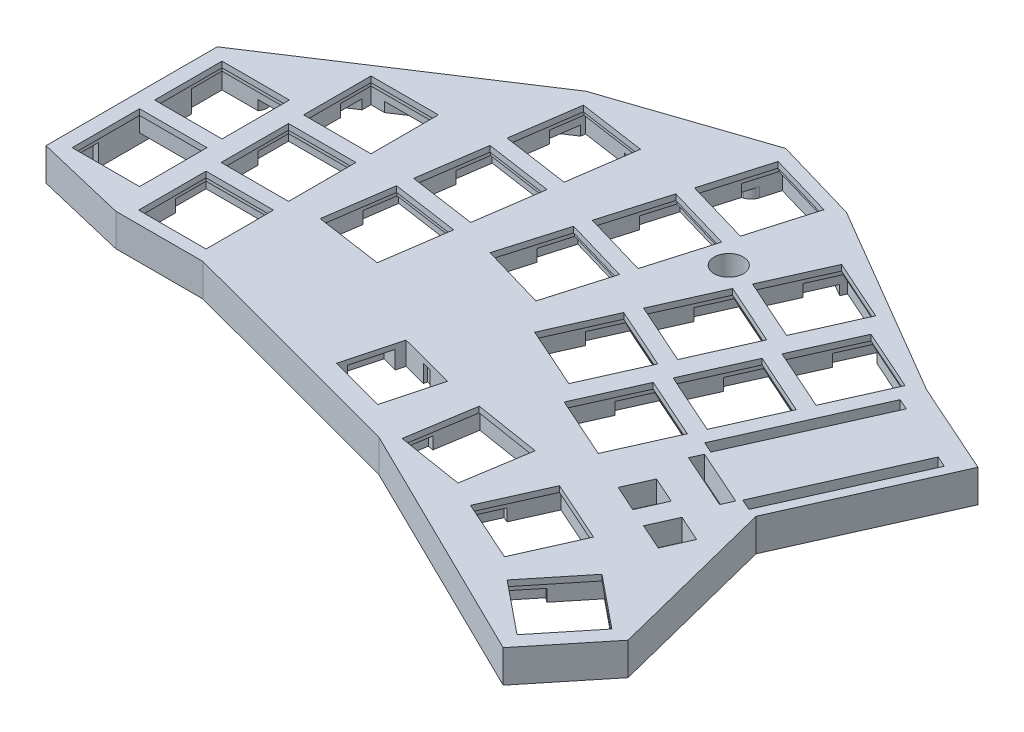
SolidWorks part; units mm, degrees
ref_plane "Front Plane" through (0, 0, 0) normal (0, 0, 1) x (1, 0, 0)
ref_plane "Top Plane" through (0, 0, 0) normal (0, 1, 0) x (1, 0, 0)
ref_plane "Right Plane" through (0, 0, 0) normal (1, 0, 0) x (0, 0, -1)
sketch "Ergogen Drawing" plane through (0, 0, 0) normal (0, 1, 0) x (1, 0, 0)
  line L0 (0.027, 17.9992) -> (18.027, 17.9992)
  line L1 (18.027, 17.9992) -> (18.027, -0.0008)
  line L2 (18.027, -0.0008) -> (0.027, -0.0008)
  line L3 (0.027, -0.0008) -> (0.027, 17.9992)
  line L4 (0.027, 34.9992) -> (18.027, 34.9992)
  line L5 (18.027, 34.9992) -> (18.027, 16.9992)
  line L6 (18.027, 16.9992) -> (0.027, 16.9992)
  line L7 (0.027, 16.9992) -> (0.027, 34.9992)
  line L8 (18.027, 15.9992) -> (36.027, 15.9992)
  line L9 (36.027, 15.9992) -> (36.027, -2.0008)
  line L10 (36.027, -2.0008) -> (18.027, -2.0008)
  line L11 (18.027, -2.0008) -> (18.027, 15.9992)
  line L12 (18.027, 32.9992) -> (36.027, 32.9992)
  line L13 (36.027, 32.9992) -> (36.027, 14.9992)
  line L14 (36.027, 14.9992) -> (18.027, 14.9992)
  line L15 (18.027, 14.9992) -> (18.027, 32.9992)
  line L16 (18.027, 49.9992) -> (36.027, 49.9992)
  line L17 (36.027, 49.9992) -> (36.027, 31.9992)
  line L18 (36.027, 31.9992) -> (18.027, 31.9992)
  line L19 (18.027, 31.9992) -> (18.027, 49.9992)
  line L20 (41.3768, 32.6051) -> (59.3329, 31.3495)
  line L21 (59.3329, 31.3495) -> (58.0773, 13.3933)
  line L22 (58.0773, 13.3933) -> (40.1211, 14.6489)
  line L23 (40.1211, 14.6489) -> (41.3768, 32.6051)
  line L24 (42.5626, 49.5637) -> (60.5188, 48.3081)
  line L25 (60.5188, 48.3081) -> (59.2631, 30.3519)
  line L26 (59.2631, 30.3519) -> (41.307, 31.6075)
  line L27 (41.307, 31.6075) -> (42.5626, 49.5637)
  line L28 (43.7485, 66.5223) -> (61.7046, 65.2667)
  line L29 (61.7046, 65.2667) -> (60.449, 47.3105)
  line L30 (60.449, 47.3105) -> (42.4929, 48.5661)
  line L31 (42.4929, 48.5661) -> (43.7485, 66.5223)
  line L32 (66.0898, 43.7082) -> (83.8507, 40.7838)
  line L33 (83.8507, 40.7838) -> (80.9263, 23.023)
  line L34 (80.9263, 23.023) -> (63.1655, 25.9473)
  line L35 (63.1655, 25.9473) -> (66.0898, 43.7082)
  line L36 (68.8517, 60.4823) -> (86.6126, 57.558)
  line L37 (86.6126, 57.558) -> (83.6882, 39.7971)
  line L38 (83.6882, 39.7971) -> (65.9274, 42.7215)
  line L39 (65.9274, 42.7215) -> (68.8517, 60.4823)
  line L40 (71.6136, 77.2565) -> (89.3745, 74.3321)
  line L41 (89.3745, 74.3321) -> (86.4501, 56.5713)
  line L42 (86.4501, 56.5713) -> (68.6893, 59.4956)
  line L43 (68.6893, 59.4956) -> (71.6136, 77.2565)
  line L44 (88.5581, 32.769) -> (105.9366, 28.0799)
  line L45 (105.9366, 28.0799) -> (101.2475, 10.7014)
  line L46 (101.2475, 10.7014) -> (83.869, 15.3905)
  line L47 (83.869, 15.3905) -> (88.5581, 32.769)
  line L48 (92.9866, 49.182) -> (110.3652, 44.4929)
  line L49 (110.3652, 44.4929) -> (105.6761, 27.1144)
  line L50 (105.6761, 27.1144) -> (88.2976, 31.8035)
  line L51 (88.2976, 31.8035) -> (92.9866, 49.182)
  line L52 (97.4152, 65.595) -> (114.7937, 60.906)
  line L53 (114.7937, 60.906) -> (110.1046, 43.5274)
  line L54 (110.1046, 43.5274) -> (92.7261, 48.2165)
  line L55 (92.7261, 48.2165) -> (97.4152, 65.595)
  line L56 (107.0448, 26.9674) -> (124.0477, 21.0597)
  line L57 (124.0477, 21.0597) -> (118.14, 4.0568)
  line L58 (118.14, 4.0568) -> (101.1371, 9.9645)
  line L59 (101.1371, 9.9645) -> (107.0448, 26.9674)
  line L60 (112.6243, 43.0257) -> (129.6273, 37.118)
  line L61 (129.6273, 37.118) -> (123.7195, 20.1151)
  line L62 (123.7195, 20.1151) -> (106.7166, 26.0228)
  line L63 (106.7166, 26.0228) -> (112.6243, 43.0257)
  line L64 (118.2039, 59.084) -> (135.2068, 53.1763)
  line L65 (135.2068, 53.1763) -> (129.299, 36.1734)
  line L66 (129.299, 36.1734) -> (112.2961, 42.0811)
  line L67 (112.2961, 42.0811) -> (118.2039, 59.084)
  line L68 (95.4197, 6.4051) -> (112.5714, 0.9445)
  line L69 (112.5714, 0.9445) -> (107.1108, -16.2072)
  line L70 (107.1108, -16.2072) -> (89.959, -10.7466)
  line L71 (89.959, -10.7466) -> (95.4197, 6.4051)
  line L72 (116.0129, -0.5249) -> (131.9353, -8.9198)
  line L73 (131.9353, -8.9198) -> (123.5404, -24.8423)
  line L74 (123.5404, -24.8423) -> (107.6179, -16.4473)
  line L75 (107.6179, -16.4473) -> (116.0129, -0.5249)
  line L76 (135.0644, -10.9721) -> (149.2602, -22.0392)
  line L77 (149.2602, -22.0392) -> (138.1931, -36.235)
  line L78 (138.1931, -36.235) -> (123.9973, -25.1679)
  line L79 (123.9973, -25.1679) -> (135.0644, -10.9721)
sketch "Layout Based on OG" plane through (0, 0, 0) normal (0, 1, 0) x (1, 0, 0)
  line L0 (0, 0) -> (0, 17) construction
  line L1 (0, 17) -> (18, 17) construction
  line L2 (18, 17) -> (18, 0) construction
  line L3 (18, 0) -> (0, 0) construction
  line L4 (2.05, 1.55) -> (2.05, 15.45)
  line L5 (2.05, 15.45) -> (15.95, 15.45)
  line L6 (15.95, 15.45) -> (15.95, 1.55)
  line L7 (15.95, 1.55) -> (2.05, 1.55)
  line L8 (109.1798, 58.6066) -> (27, -125.5436) construction
  line L9 (27, 46.7087) -> (27, -125.5436) construction
  line L10 (84.3863, 71.4039) -> (27, -125.5436) construction
  line L11 (54.2678, 62.3831) -> (27, -125.5436) construction
  line L12 (44.7261, 45.0233) -> (58.4821, 43.0274)
  line L13 (2.05, 18.55) -> (15.95, 18.55)
  line L14 (2.05, 18.55) -> (2.05, 32.45)
  line L15 (2.05, 32.45) -> (15.95, 32.45)
  line L16 (15.95, 18.55) -> (15.95, 32.45)
  line L17 (20.05, 31.2587) -> (33.95, 31.2587)
  line L18 (20.05, 31.2587) -> (20.05, 45.1587)
  line L19 (20.05, 45.1587) -> (33.95, 45.1587)
  line L20 (33.95, 31.2587) -> (33.95, 45.1587)
  line L21 (33.95, 28.1587) -> (20.05, 28.1587)
  line L22 (33.95, 28.1587) -> (33.95, 14.2587)
  line L23 (33.95, 14.2587) -> (20.05, 14.2587)
  line L24 (20.05, 28.1587) -> (20.05, 14.2587)
  line L25 (20.05, -2.7413) -> (33.95, -2.7413)
  line L26 (20.05, -2.7413) -> (20.05, 11.1587)
  line L27 (20.05, 11.1587) -> (33.95, 11.1587)
  line L28 (33.95, -2.7413) -> (33.95, 11.1587)
  line L29 (44.7261, 45.0233) -> (42.7302, 31.2674)
  line L30 (58.4821, 43.0274) -> (56.4861, 29.2714)
  line L31 (42.7302, 31.2674) -> (56.4861, 29.2714)
  line L32 (42.285, 28.1995) -> (56.041, 26.2036)
  line L33 (42.285, 28.1995) -> (40.2891, 14.4436)
  line L34 (56.041, 26.2036) -> (54.045, 12.4476)
  line L35 (40.2891, 14.4436) -> (54.045, 12.4476)
  line L36 (47.1672, 61.8472) -> (60.9232, 59.8512)
  line L37 (47.1672, 61.8472) -> (45.1712, 48.0912)
  line L38 (60.9232, 59.8512) -> (58.9272, 46.0953)
  line L39 (45.1712, 48.0912) -> (58.9272, 46.0953)
  line L40 (77.2802, 71.86) -> (90.6252, 67.9716)
  line L41 (77.2802, 71.86) -> (73.3917, 58.515)
  line L42 (90.6252, 67.9716) -> (86.7368, 54.6265)
  line L43 (73.3917, 58.515) -> (86.7368, 54.6265)
  line L44 (85.8695, 51.6503) -> (72.5245, 55.5388)
  line L45 (85.8695, 51.6503) -> (81.9811, 38.3053)
  line L46 (72.5245, 55.5388) -> (68.6361, 42.1937)
  line L47 (81.9811, 38.3053) -> (68.6361, 42.1937)
  line L48 (67.7688, 39.2175) -> (81.1139, 35.329)
  line L49 (67.7688, 39.2175) -> (63.8804, 25.8725)
  line L50 (81.1139, 35.329) -> (77.2254, 21.984)
  line L51 (63.8804, 25.8725) -> (77.2254, 21.984)
  line L52 (102.2015, 60.0235) -> (114.8949, 54.3589)
  line L53 (102.2015, 60.0235) -> (96.5369, 47.3301)
  line L54 (114.8949, 54.3589) -> (109.2302, 41.6655)
  line L55 (96.5369, 47.3301) -> (109.2302, 41.6655)
  line L56 (107.9669, 38.8346) -> (95.2735, 44.4992)
  line L57 (107.9669, 38.8346) -> (102.3023, 26.1412)
  line L58 (95.2735, 44.4992) -> (89.6089, 31.8058)
  line L59 (102.3023, 26.1412) -> (89.6089, 31.8058)
  line L60 (101.039, 23.3103) -> (88.3456, 28.9749)
  line L61 (101.039, 23.3103) -> (95.3744, 10.6169)
  line L62 (88.3456, 28.9749) -> (82.681, 16.2815)
  line L63 (95.3744, 10.6169) -> (82.681, 16.2815)
  line L64 (117.7053, 50.5958) -> (130.3987, 44.9312)
  line L65 (117.7053, 50.5958) -> (112.0407, 37.9024)
  line L66 (130.3987, 44.9312) -> (124.734, 32.2378)
  line L67 (112.0407, 37.9024) -> (124.734, 32.2378)
  line L68 (123.4707, 29.4069) -> (110.7773, 35.0715)
  line L69 (123.4707, 29.4069) -> (117.8061, 16.7135)
  line L70 (110.7773, 35.0715) -> (105.1127, 22.3782)
  line L71 (117.8061, 16.7135) -> (105.1127, 22.3782)
  line L72 (116.5428, 13.8826) -> (103.8494, 19.5473)
  line L73 (116.5428, 13.8826) -> (110.8782, 1.1892)
  line L74 (103.8494, 19.5473) -> (98.1848, 6.8539)
  line L75 (110.8782, 1.1892) -> (98.1848, 6.8539)
  line L76 (90.1692, -2.6429) -> (103.8962, -4.8292)
  line L77 (90.1692, -2.6429) -> (87.9829, -16.3699)
  line L78 (103.8962, -4.8292) -> (101.7099, -18.5562)
  line L79 (87.9829, -16.3699) -> (101.7099, -18.5562)
  line L80 (112.6329, -8.5638) -> (125.3263, -14.2284)
  line L81 (112.6329, -8.5638) -> (106.9683, -21.2572)
  line L82 (125.3263, -14.2284) -> (119.6617, -26.9218)
  line L83 (106.9683, -21.2572) -> (119.6617, -26.9218)
  line L84 (132.8305, -19.9983) -> (143.6253, -28.7552)
  line L85 (132.8305, -19.9983) -> (124.0737, -30.7931)
  line L86 (143.6253, -28.7552) -> (134.8684, -39.55)
  line L87 (124.0737, -30.7931) -> (134.8684, -39.55)
  line L88 (0, 0) -> (0, 34) construction
  line L89 (0, 34) -> (18, 46.7087) construction
  line L90 (18, 46.7087) -> (45.361, 63.6755) construction
  line L91 (45.361, 63.6755) -> (75.7456, 73.9216) construction
  line L92 (75.7456, 73.9216) -> (93.027, 68.8862) construction
  line L93 (93.027, 68.8862) -> (117.3986, 54.9389) construction
  line L94 (117.3986, 54.9389) -> (132.9024, 45.5112) construction
  line L95 (146.1938, -28.843) -> (135.484, -42.0452) construction
  line L96 (135.484, -42.0452) -> (85.7146, -17.5782) construction
  line L97 (0, 0) -> (18, -4.2913) construction
  line L98 (132.9024, 45.5112) -> (119.0465, 14.4627) construction
  line L99 (18, -4.2913) -> (36, -4.2913) construction
  line L100 (36, -4.2913) -> (85.7146, -17.5782) construction
  line L101 (119.0465, 14.4627) -> (137.3104, 6.3121) construction
  line L102 (137.3104, 6.3121) -> (151.1662, 37.3607) construction
  line L103 (151.1662, 37.3607) -> (132.9024, 45.5112) construction
  line L104 (146.1938, -28.843) -> (137.3104, 6.3121) construction
  line L105 (137.3104, 6.3121) -> (151.1662, 37.3607) construction
  line L106 (151.1662, 37.3607) -> (132.9024, 45.5112) construction
  line L107 (119.9597, 14.0551) -> (132.3892, 41.9075)
  line L108 (132.3892, 41.9075) -> (134.6722, 40.8887)
  line L109 (134.6722, 40.8887) -> (122.2427, 13.0363)
  line L110 (122.2427, 13.0363) -> (119.9597, 14.0551)
  line L111 (136.3972, 6.7197) -> (148.8267, 34.5721)
  line L112 (148.8267, 34.5721) -> (146.5437, 35.5909)
  line L113 (146.5437, 35.5909) -> (134.1142, 7.7385)
  line L114 (134.1142, 7.7385) -> (136.3972, 6.7197)
  line L115 (79.4058, -12.7868) -> (67.8127, -9.6883)
  line L116 (67.8127, -9.6883) -> (70.8336, 1.6149)
  line L117 (70.8336, 1.6149) -> (82.4267, -1.4835)
  line L118 (82.4267, -1.4835) -> (79.4058, -12.7868)
  line L119 (97.0327, -3.7361) -> (94.8464, -17.4631) construction
  line L120 (118.9913, -2.8379) -> (121.4364, 2.6412)
  line L121 (121.4364, 2.6412) -> (126.9156, 0.1961)
  line L122 (76.6302, 0.0657) -> (73.6092, -11.2375) construction
  line L123 (126.9156, 0.1961) -> (124.4704, -5.2831)
  line L124 (124.4704, -5.2831) -> (118.9913, -2.8379)
  line L125 (128.4611, -7.064) -> (130.9062, -1.5848)
  line L126 (130.9062, -1.5848) -> (136.3854, -4.03)
  line L127 (136.3854, -4.03) -> (133.9402, -9.5091)
  line L128 (133.9402, -9.5091) -> (128.4611, -7.064)
  line L137 (124.176, 1.4187) -> (121.7308, -4.0605) construction
  line L138 (133.6458, -2.8074) -> (131.2006, -8.2865) construction
  line L139 (126.7317, 7.1456) -> (128.1784, 10.3874) construction
  line L140 (135.0103, 42.8732) -> (147.795, 37.1678) construction
  line L141 (147.795, 37.1678) -> (133.1241, 4.2929) construction
  line L142 (133.1241, 4.2929) -> (120.3393, 9.9982) construction
  line L143 (120.3393, 9.9982) -> (135.0103, 42.8732) construction
  line L144 (120.9512, 9.7252) -> (121.97, 12.0082)
  line L145 (121.97, 12.0082) -> (133.531, 6.8489)
  line L146 (133.531, 6.8489) -> (132.5122, 4.5659)
  line L147 (132.5122, 4.5659) -> (120.9512, 9.7252)
  line L148 (126.9156, 0.1961) -> (140.3735, -5.8097) construction
  line L164 (-1, 34.5181) -> (-1, -0.7896)
  line L165 (-1, -0.7896) -> (17.8824, -5.2913)
  line L166 (17.8824, -5.2913) -> (35.8687, -5.2913)
  line L167 (35.8687, -5.2913) -> (85.3615, -18.5189)
  line L168 (85.3615, -18.5189) -> (135.7583, -43.2944)
  line L169 (135.7583, -43.2944) -> (147.2861, -29.0838)
  line L170 (147.2861, -29.0838) -> (138.3648, 6.2211)
  line L171 (138.3648, 6.2211) -> (152.487, 37.8664)
  line L172 (152.487, 37.8664) -> (133.3678, 46.3986)
  line L173 (133.3678, 46.3986) -> (117.9068, 55.8002) construction
  line L174 (117.9068, 55.8002) -> (93.4207, 69.8131) construction
  line L175 (93.4207, 69.8131) -> (75.7238, 74.9696)
  line L176 (75.7238, 74.9696) -> (44.9321, 64.5862)
  line L177 (44.9321, 64.5862) -> (17.4476, 47.5429) construction
  line L178 (17.4476, 47.5429) -> (-1, 34.5181) construction
  line L179 (-1, 34.5181) -> (44.9321, 64.5862)
  line L180 (133.3678, 46.3986) -> (93.4207, 69.8131)
  line L181 (27, -125.5436) -> (90.7493, 48.2155) construction
  circle A0 centre (143.0056, -24.3895) radius 2 construction
  circle A1 centre (143.0056, -24.3895) radius 1
  circle A2 centre (98.5143, -21.642) radius 2 construction
  circle A3 centre (98.5143, -21.642) radius 1
  circle A6 centre (17.05, -2.0087) radius 2 construction
  circle A7 centre (17.05, -2.0087) radius 1
  circle A8 centre (5.901, 35.45) radius 2 construction
  circle A9 centre (5.901, 35.45) radius 1
  circle A10 centre (72.7535, 70.802) radius 2 construction
  circle A11 centre (72.7535, 70.802) radius 1
  circle A12 centre (145.3286, 37.7757) radius 2 construction
  circle A13 centre (145.3286, 37.7757) radius 1
  circle A14 centre (90.7493, 48.2155) radius 3
  point P10 (110.8277, 18.1304)
  point P11 (117.7557, 33.6547)
  point P128 (75.1197, -5.5859)
  point P129 (95.9395, -10.5996)
  point P146 (127.7505, 9.4285)
  point P148 (128.1784, 10.3874)
  point P150 (122.9534, -1.3209)
  line B0 (18, 29.7087) -> (18, 46.7087) construction
  line B1 (18, 46.7087) -> (36, 46.7087) construction
  line B2 (36, 46.7087) -> (36, 29.7087) construction
  line B3 (36, 29.7087) -> (18, 29.7087) construction
  line B4 (20.05, 31.2587) -> (20.05, 45.1587) construction
  line B5 (20.05, 45.1587) -> (33.95, 45.1587) construction
  line B6 (33.95, 45.1587) -> (33.95, 31.2587) construction
  line B7 (33.95, 31.2587) -> (20.05, 31.2587) construction
  line B8 (18, 12.7087) -> (18, 29.7087) construction
  line B9 (18, 29.7087) -> (36, 29.7087) construction
  line B10 (36, 29.7087) -> (36, 12.7087) construction
  line B11 (36, 12.7087) -> (18, 12.7087) construction
  line B12 (20.05, 14.2587) -> (20.05, 28.1587) construction
  line B13 (20.05, 28.1587) -> (33.95, 28.1587) construction
  line B14 (33.95, 28.1587) -> (33.95, 14.2587) construction
  line B15 (33.95, 14.2587) -> (20.05, 14.2587) construction
  line B16 (18, -4.2913) -> (18, 12.7087) construction
  line B17 (18, 12.7087) -> (36, 12.7087) construction
  line B18 (36, 12.7087) -> (36, -4.2913) construction
  line B19 (36, -4.2913) -> (18, -4.2913) construction
  line B20 (20.05, -2.7413) -> (20.05, 11.1587) construction
  line B21 (20.05, 11.1587) -> (33.95, 11.1587) construction
  line B22 (33.95, 11.1587) -> (33.95, -2.7413) construction
  line B23 (33.95, -2.7413) -> (20.05, -2.7413) construction
  line B24 (42.9199, 46.8516) -> (45.361, 63.6755) construction
  line B25 (45.361, 63.6755) -> (63.1745, 61.0908) construction
  line B26 (63.1745, 61.0908) -> (60.7334, 44.267) construction
  line B27 (60.7334, 44.267) -> (42.9199, 46.8516) construction
  line B28 (45.1712, 48.0912) -> (47.1672, 61.8472) construction
  line B29 (47.1672, 61.8472) -> (60.9232, 59.8512) construction
  line B30 (60.9232, 59.8512) -> (58.9272, 46.0953) construction
  line B31 (58.9272, 46.0953) -> (45.1712, 48.0912) construction
  line B32 (40.4788, 30.0278) -> (42.9199, 46.8516) construction
  line B33 (42.9199, 46.8516) -> (60.7334, 44.267) construction
  line B34 (60.7334, 44.267) -> (58.2923, 27.4431) construction
  line B35 (58.2923, 27.4431) -> (40.4788, 30.0278) construction
  line B36 (42.7302, 31.2674) -> (44.7261, 45.0233) construction
  line B37 (44.7261, 45.0233) -> (58.4821, 43.0274) construction
  line B38 (58.4821, 43.0274) -> (56.4861, 29.2714) construction
  line B39 (56.4861, 29.2714) -> (42.7302, 31.2674) construction
  line B40 (38.0377, 13.204) -> (40.4788, 30.0278) construction
  line B41 (40.4788, 30.0278) -> (58.2923, 27.4431) construction
  line B42 (58.2923, 27.4431) -> (55.8512, 10.6193) construction
  line B43 (55.8512, 10.6193) -> (38.0377, 13.204) construction
  line B44 (40.2891, 14.4436) -> (42.285, 28.1995) construction
  line B45 (42.285, 28.1995) -> (56.041, 26.2036) construction
  line B46 (56.041, 26.2036) -> (54.045, 12.4476) construction
  line B47 (54.045, 12.4476) -> (40.2891, 14.4436) construction
  line B48 (70.99, 57.6004) -> (75.7456, 73.9216) construction
  line B49 (75.7456, 73.9216) -> (93.027, 68.8862) construction
  line B50 (93.027, 68.8862) -> (88.2713, 52.5649) construction
  line B51 (88.2713, 52.5649) -> (70.99, 57.6004) construction
  line B52 (73.3917, 58.515) -> (77.2802, 71.86) construction
  line B53 (77.2802, 71.86) -> (90.6252, 67.9716) construction
  line B54 (90.6252, 67.9716) -> (86.7368, 54.6265) construction
  line B55 (86.7368, 54.6265) -> (73.3917, 58.515) construction
  line B56 (66.2343, 41.2791) -> (70.99, 57.6004) construction
  line B57 (70.99, 57.6004) -> (88.2713, 52.5649) construction
  line B58 (88.2713, 52.5649) -> (83.5156, 36.2437) construction
  line B59 (83.5156, 36.2437) -> (66.2343, 41.2791) construction
  line B60 (68.6361, 42.1937) -> (72.5245, 55.5388) construction
  line B61 (72.5245, 55.5388) -> (85.8695, 51.6503) construction
  line B62 (85.8695, 51.6503) -> (81.9811, 38.3053) construction
  line B63 (81.9811, 38.3053) -> (68.6361, 42.1937) construction
  line B64 (61.4786, 24.9578) -> (66.2343, 41.2791) construction
  line B65 (66.2343, 41.2791) -> (83.5156, 36.2437) construction
  line B66 (83.5156, 36.2437) -> (78.76, 19.9224) construction
  line B67 (78.76, 19.9224) -> (61.4786, 24.9578) construction
  line B68 (63.8804, 25.8725) -> (67.7688, 39.2175) construction
  line B69 (67.7688, 39.2175) -> (81.1139, 35.329) construction
  line B70 (81.1139, 35.329) -> (77.2254, 21.984) construction
  line B71 (77.2254, 21.984) -> (63.8804, 25.8725) construction
  line B72 (80.1772, 15.7015) -> (87.1052, 31.2258) construction
  line B73 (87.1052, 31.2258) -> (103.5427, 23.8903) construction
  line B74 (103.5427, 23.8903) -> (96.6147, 8.366) construction
  line B75 (96.6147, 8.366) -> (80.1772, 15.7015) construction
  line B76 (82.681, 16.2815) -> (88.3456, 28.9749) construction
  line B77 (88.3456, 28.9749) -> (101.039, 23.3103) construction
  line B78 (101.039, 23.3103) -> (95.3744, 10.6169) construction
  line B79 (95.3744, 10.6169) -> (82.681, 16.2815) construction
  line B80 (87.1052, 31.2258) -> (94.0331, 46.7501) construction
  line B81 (94.0331, 46.7501) -> (110.4706, 39.4146) construction
  line B82 (110.4706, 39.4146) -> (103.5427, 23.8903) construction
  line B83 (103.5427, 23.8903) -> (87.1052, 31.2258) construction
  line B84 (89.6089, 31.8058) -> (95.2735, 44.4992) construction
  line B85 (95.2735, 44.4992) -> (107.9669, 38.8346) construction
  line B86 (107.9669, 38.8346) -> (102.3023, 26.1412) construction
  line B87 (102.3023, 26.1412) -> (89.6089, 31.8058) construction
  line B88 (94.0331, 46.7501) -> (100.9611, 62.2744) construction
  line B89 (100.9611, 62.2744) -> (117.3986, 54.9389) construction
  line B90 (117.3986, 54.9389) -> (110.4706, 39.4146) construction
  line B91 (110.4706, 39.4146) -> (94.0331, 46.7501) construction
  line B92 (96.5369, 47.3301) -> (102.2015, 60.0235) construction
  line B93 (102.2015, 60.0235) -> (114.8949, 54.3589) construction
  line B94 (114.8949, 54.3589) -> (109.2302, 41.6655) construction
  line B95 (109.2302, 41.6655) -> (96.5369, 47.3301) construction
  line B96 (109.5369, 37.3224) -> (116.4649, 52.8467) construction
  line B97 (116.4649, 52.8467) -> (132.9024, 45.5112) construction
  line B98 (132.9024, 45.5112) -> (125.9744, 29.9869) construction
  line B99 (125.9744, 29.9869) -> (109.5369, 37.3224) construction
  line B100 (112.0407, 37.9024) -> (117.7053, 50.5958) construction
  line B101 (117.7053, 50.5958) -> (130.3987, 44.9312) construction
  line B102 (130.3987, 44.9312) -> (124.734, 32.2378) construction
  line B103 (124.734, 32.2378) -> (112.0407, 37.9024) construction
  line B104 (102.609, 21.7981) -> (109.5369, 37.3224) construction
  line B105 (109.5369, 37.3224) -> (125.9744, 29.9869) construction
  line B106 (125.9744, 29.9869) -> (119.0465, 14.4627) construction
  line B107 (119.0465, 14.4627) -> (102.609, 21.7981) construction
  line B108 (105.1127, 22.3782) -> (110.7773, 35.0715) construction
  line B109 (110.7773, 35.0715) -> (123.4707, 29.4069) construction
  line B110 (123.4707, 29.4069) -> (117.8061, 16.7135) construction
  line B111 (117.8061, 16.7135) -> (105.1127, 22.3782) construction
  line B112 (95.6811, 6.2738) -> (102.609, 21.7981) construction
  line B113 (102.609, 21.7981) -> (119.0465, 14.4627) construction
  line B114 (119.0465, 14.4627) -> (112.1185, -1.0616) construction
  line B115 (112.1185, -1.0616) -> (95.6811, 6.2738) construction
  line B116 (98.1848, 6.8539) -> (103.8494, 19.5473) construction
  line B117 (103.8494, 19.5473) -> (116.5428, 13.8826) construction
  line B118 (116.5428, 13.8826) -> (110.8782, 1.1892) construction
  line B119 (110.8782, 1.1892) -> (98.1848, 6.8539) construction
  line B120 (104.4646, -21.8372) -> (111.3925, -6.3129) construction
  line B121 (111.3925, -6.3129) -> (127.83, -13.6484) construction
  line B122 (127.83, -13.6484) -> (120.9021, -29.1727) construction
  line B123 (120.9021, -29.1727) -> (104.4646, -21.8372) construction
  line B124 (106.9683, -21.2572) -> (112.6329, -8.5638) construction
  line B125 (112.6329, -8.5638) -> (125.3263, -14.2284) construction
  line B126 (125.3263, -14.2284) -> (119.6617, -26.9218) construction
  line B127 (119.6617, -26.9218) -> (106.9683, -21.2572) construction
  line B128 (85.7146, -17.5782) -> (88.3885, -0.7898) construction
  line B129 (88.3885, -0.7898) -> (106.1645, -3.621) construction
  line B130 (106.1645, -3.621) -> (103.4906, -20.4094) construction
  line B131 (103.4906, -20.4094) -> (85.7146, -17.5782) construction
  line B132 (87.9829, -16.3699) -> (90.1692, -2.6429) construction
  line B133 (90.1692, -2.6429) -> (103.8962, -4.8292) construction
  line B134 (103.8962, -4.8292) -> (101.7099, -18.5562) construction
  line B135 (101.7099, -18.5562) -> (87.9829, -16.3699) construction
  line B136 (121.5051, -30.7054) -> (132.215, -17.5031) construction
  line B137 (132.215, -17.5031) -> (146.1938, -28.843) construction
  line B138 (146.1938, -28.843) -> (135.484, -42.0452) construction
  line B139 (135.484, -42.0452) -> (121.5051, -30.7054) construction
  line B140 (124.0737, -30.7931) -> (132.8305, -19.9983) construction
  line B141 (132.8305, -19.9983) -> (143.6253, -28.7552) construction
  line B142 (143.6253, -28.7552) -> (134.8684, -39.55) construction
  line B143 (134.8684, -39.55) -> (124.0737, -30.7931) construction
  line B144 (0, 17) -> (0, 34) construction
  line B145 (0, 34) -> (18, 34) construction
  line B146 (18, 34) -> (18, 17) construction
  line B147 (18, 17) -> (0, 17) construction
  line B148 (2.05, 18.55) -> (2.05, 32.45) construction
  line B149 (2.05, 32.45) -> (15.95, 32.45) construction
  line B150 (15.95, 32.45) -> (15.95, 18.55) construction
  line B151 (15.95, 18.55) -> (2.05, 18.55) construction
  dimension "D46" = 4
  dimension "D47" = 2
  dimension "D48" = 3
  dimension "D52" = 4
  dimension "D53" = 2
  dimension "D54" = 4
  dimension "D55" = 2
  dimension "D57" = 4
  dimension "D58" = 2
  dimension "D60" = 4
  dimension "D61" = 2
  dimension "D63" = 4
  dimension "D64" = 2
  dimension "D51" = 3
  dimension "D83" = 6
  dimension "D1" = 18
  dimension "D2" = 17
  dimension "D3" = 13.9
  dimension "D4" = 13.9
  dimension "D5" = 2.05
  dimension "D6" = 1.55
  dimension "D7" = 205.1378
  dimension "D8" = 201.6553
  dimension "D9" = 189.8947
  dimension "D10" = 8.256
  dimension "D11" = 15
  dimension "D12" = 15
  dimension "D13" = 1.4278
  dimension "D14" = 0.974
  dimension "D15" = 1.5327
  dimension "D16" = 0.6031
  dimension "D17" = 5.9541
  dimension "D18" = 2.5593
  dimension "D19" = 7.805
  dimension "D20" = 7.989
  dimension "D21" = 172.2524
  dimension "D22" = 2.2911
  dimension "D23" = 4.2913
  dimension "D24" = 34
  dimension "D25" = 20
  dimension "D26" = 30.5
  dimension "D27" = 2.5
  dimension "D28" = 1
  dimension "D29" = 2.5
  dimension "D30" = 30.5
  dimension "D31" = 18
  dimension "D32" = 11.7
  dimension "D33" = 12
  dimension "D34" = 3
  dimension "D35" = 21.415
  dimension "D36" = 6
  dimension "D37" = 6
  dimension "D38" = 6
  dimension "D39" = 6
  dimension "D40" = 14
  dimension "D41" = 36
  dimension "D42" = 12.66
  dimension "D43" = 2.5
  dimension "D44" = 9.27
  dimension "D45" = 4.37
  dimension "D49" = 3
  dimension "D50" = 3
  dimension "D56" = 3
  dimension "D59" = 3
  dimension "D62" = 3
  dimension "D65" = 3
  dimension "D66" = 3
  dimension "D67" = 1
  dimension "D68" = 1
  dimension "D69" = 1
  dimension "D70" = 1
  dimension "D71" = 1
  dimension "D72" = 1
  dimension "D73" = 1
  dimension "D74" = 1
  dimension "D75" = 1
  dimension "D76" = 1
  dimension "D77" = 1
  dimension "D78" = 1
  dimension "D79" = 1
  dimension "D80" = 1
  dimension "D81" = 1
  dimension "D82" = 3.902
sketch_block_instance "Block-ChocSwitchCutout-3"
sketch_block "Block-ChocSwitchCutout" parameters "D1"=18, "D2"=17, "D3"=13.9, "D4"=13.9, "D5"=2.05, "D6"=1.55
sketch_block_instance "Block-ChocSwitchCutout-4"
sketch_block_instance "Block-ChocSwitchCutout-5"
sketch_block_instance "Block-ChocSwitchCutout-6"
sketch_block_instance "Block-ChocSwitchCutout-7"
sketch_block_instance "Block-ChocSwitchCutout-8"
sketch_block_instance "Block-ChocSwitchCutout-9"
sketch_block_instance "Block-ChocSwitchCutout-10"
sketch_block_instance "Block-ChocSwitchCutout-11"
sketch_block_instance "Block-ChocSwitchCutout-20"
sketch_block_instance "Block-ChocSwitchCutout-23"
sketch_block_instance "Block-ChocSwitchCutout-24"
sketch_block_instance "Block-ChocSwitchCutout-27"
sketch_block_instance "Block-ChocSwitchCutout-28"
sketch_block_instance "Block-ChocSwitchCutout-29"
sketch_block_instance "Block-ChocSwitchCutout-32"
sketch_block_instance "Block-ChocSwitchCutout-33"
sketch_block_instance "Block-ChocSwitchCutout-34"
sketch_block_instance "Block-ChocSwitchCutout-37"
other "AlignGroup1"
extrude "Top Plate" add sketch "Layout Based on OG" along normal blind 1.2 contours L105 L106 L94 L93 L92 L91 L90 L89 L88 L97 L99 L100 L96 L95 L104 L73 L75 L74 L72 L69 L71 L70 L68 L61 L63 L62 L60 L57 L59 L58 L56 L45 L47 L46 L44 L6 L7 L4 L5 L16 L13 L14 L15 | A9 | A7 | A3 | A1 | A13 | A11 region at (81.1823, 0, -18.7965) region at (143.0056, 0, 24.3895) region at (98.5143, 0, 21.642) region at (17.05, 0, 2.0087) region at (5.901, 0, -35.45) region at (72.7535, 0, -70.802) region at (145.3286, 0, -37.7757)
sketch "Sketch1" plane through (0, 0, 0) normal (0, -1, 0) x (1, 0, 0)
  line L0 (124.9363, -31.7095) -> (130.927, -45.1335)
  line L1 (130.927, -45.1335) -> (117.503, -51.1241)
  line L2 (117.503, -51.1241) -> (111.5124, -37.7002)
  line L3 (111.5124, -37.7002) -> (124.9363, -31.7095)
  line L4 (118.0084, -16.1852) -> (123.999, -29.6092)
  line L5 (117.7053, -50.5958) -> (130.3987, -44.9312) construction
  line L6 (123.999, -29.6092) -> (110.5751, -35.5998)
  line L7 (117.7053, -50.5958) -> (112.0407, -37.9024) construction
  line L8 (110.5751, -35.5998) -> (104.5844, -22.1759)
  line L9 (104.5844, -22.1759) -> (118.0084, -16.1852)
  line L10 (123.4707, -29.4069) -> (117.8061, -16.7135) construction
  line L11 (111.0804, -0.661) -> (117.0711, -14.0849)
  line L12 (117.8061, -16.7135) -> (105.1127, -22.3782) construction
  line L13 (117.0711, -14.0849) -> (103.6471, -20.0755)
  line L14 (103.6471, -20.0755) -> (97.6565, -6.6516)
  line L15 (97.6565, -6.6516) -> (111.0804, -0.661)
  line L16 (103.8494, -19.5473) -> (98.1848, -6.8539) construction
  line L17 (110.8782, -1.1892) -> (98.1848, -6.8539) construction
  line L18 (95.5766, -10.0886) -> (101.5673, -23.5126)
  line L19 (101.5673, -23.5126) -> (88.1433, -29.5032)
  line L20 (88.1433, -29.5032) -> (82.1527, -16.0793)
  line L21 (82.1527, -16.0793) -> (95.5766, -10.0886)
  line L22 (101.039, -23.3103) -> (88.3456, -28.9749) construction
  line L23 (101.039, -23.3103) -> (95.3744, -10.6169) construction
  line L24 (102.5046, -25.6129) -> (108.4952, -39.0369)
  line L25 (108.4952, -39.0369) -> (95.0713, -45.0275)
  line L26 (95.0713, -45.0275) -> (89.0806, -31.6036)
  line L27 (89.0806, -31.6036) -> (102.5046, -25.6129)
  line L28 (102.3023, -26.1412) -> (89.6089, -31.8058) construction
  line L29 (95.2735, -44.4992) -> (89.6089, -31.8058) construction
  line L30 (109.4325, -41.1372) -> (115.4231, -54.5612)
  line L31 (115.4231, -54.5612) -> (101.9992, -60.5518)
  line L32 (101.9992, -60.5518) -> (96.0086, -47.1279)
  line L33 (96.0086, -47.1279) -> (109.4325, -41.1372)
  line L34 (102.2015, -60.0235) -> (114.8949, -54.3589) construction
  line L35 (114.8949, -54.3589) -> (109.2302, -41.6655) construction
  line L36 (119.864, 27.4501) -> (125.8546, 14.0261)
  line L37 (125.8546, 14.0261) -> (112.4307, 8.0355)
  line L38 (112.4307, 8.0355) -> (106.44, 21.4594)
  line L39 (106.44, 21.4594) -> (119.864, 27.4501)
  line L40 (125.3263, 14.2284) -> (119.6617, 26.9218) construction
  line L41 (106.9683, 21.2572) -> (119.6617, 26.9218) construction
  line L42 (144.1879, 28.6966) -> (134.9271, 40.1126)
  line L43 (134.9271, 40.1126) -> (123.511, 30.8517)
  line L44 (123.511, 30.8517) -> (132.7719, 19.4357)
  line L45 (132.7719, 19.4357) -> (144.1879, 28.6966)
  line L46 (143.6253, 28.7552) -> (134.8684, 39.55) construction
  line L47 (132.8305, 19.9983) -> (143.6253, 28.7552) construction
  line L48 (132.8305, 19.9983) -> (124.0737, 30.7931) construction
  line L49 (104.3541, 4.4971) -> (102.042, 19.0142)
  line L50 (102.042, 19.0142) -> (87.5249, 16.702)
  line L51 (87.5249, 16.702) -> (89.8371, 2.185)
  line L52 (89.8371, 2.185) -> (104.3541, 4.4971)
  line L61 (86.3655, -51.9224) -> (82.2532, -37.8093)
  line L62 (103.8962, 4.8292) -> (101.7099, 18.5562) construction
  line L63 (82.2532, -37.8093) -> (68.1401, -41.9216)
  line L64 (87.9829, 16.3699) -> (101.7099, 18.5562) construction
  line L65 (91.1211, -68.2437) -> (87.0089, -54.1306)
  line L66 (87.0089, -54.1306) -> (72.8958, -58.2429)
  line L67 (72.8958, -58.2429) -> (77.008, -72.3559)
  line L68 (77.008, -72.3559) -> (91.1211, -68.2437)
  line L69 (61.3764, -60.1896) -> (59.2656, -45.642)
  line L70 (59.2656, -45.642) -> (44.718, -47.7528)
  line L71 (44.718, -47.7528) -> (46.8288, -62.3005)
  line L72 (46.8288, -62.3005) -> (61.3764, -60.1896)
  line L73 (34.35, -45.5587) -> (34.35, -30.8587)
  line L74 (34.35, -30.8587) -> (19.65, -30.8587)
  line L75 (19.65, -30.8587) -> (19.65, -45.5587)
  line L76 (19.65, -45.5587) -> (34.35, -45.5587)
  line L77 (90.6252, -67.9716) -> (86.7368, -54.6265) construction
  line L78 (47.1672, -61.8472) -> (45.1712, -48.0912) construction
  line L79 (33.95, -31.2587) -> (33.95, -45.1587) construction
  line L80 (73.3917, -58.515) -> (86.7368, -54.6265) construction
  line L81 (60.9232, -59.8512) -> (58.9272, -46.0953) construction
  line L82 (45.1712, -48.0912) -> (58.9272, -46.0953) construction
  line L83 (68.1401, -41.9216) -> (72.2524, -56.0347)
  line L84 (20.05, -31.2587) -> (33.95, -31.2587) construction
  line L85 (72.2524, -56.0347) -> (86.3655, -51.9224)
  line L86 (85.8695, -51.6503) -> (81.9811, -38.3053) construction
  line L87 (81.9811, -38.3053) -> (68.6361, -42.1937) construction
  line L88 (81.6098, -35.6012) -> (77.4976, -21.4881)
  line L89 (77.4976, -21.4881) -> (63.3845, -25.6003)
  line L90 (63.3845, -25.6003) -> (67.4967, -39.7134)
  line L91 (67.4967, -39.7134) -> (81.6098, -35.6012)
  line L92 (81.1139, -35.329) -> (77.2254, -21.984) construction
  line L93 (63.8804, -25.8725) -> (77.2254, -21.984) construction
  line L94 (58.9353, -43.3658) -> (56.8245, -28.8181)
  line L95 (56.8245, -28.8181) -> (42.2769, -30.929)
  line L96 (42.2769, -30.929) -> (44.3877, -45.4766)
  line L97 (44.3877, -45.4766) -> (58.9353, -43.3658)
  line L98 (58.4821, -43.0274) -> (56.4861, -29.2714) construction
  line L99 (42.7302, -31.2674) -> (56.4861, -29.2714) construction
  line L100 (56.4943, -26.542) -> (54.3834, -11.9943)
  line L101 (54.3834, -11.9943) -> (39.8358, -14.1052)
  line L102 (39.8358, -14.1052) -> (41.9466, -28.6528)
  line L103 (41.9466, -28.6528) -> (56.4943, -26.542)
  line L104 (56.041, -26.2036) -> (54.045, -12.4476) construction
  line L105 (40.2891, -14.4436) -> (54.045, -12.4476) construction
  line L106 (34.35, -28.5587) -> (34.35, -13.8587)
  line L107 (34.35, -13.8587) -> (19.65, -13.8587)
  line L108 (19.65, -13.8587) -> (19.65, -28.5587)
  line L109 (19.65, -28.5587) -> (34.35, -28.5587)
  line L110 (33.95, -28.1587) -> (33.95, -14.2587) construction
  line L111 (33.95, -14.2587) -> (20.05, -14.2587) construction
  line L112 (34.35, -11.5587) -> (34.35, 3.1413)
  line L113 (34.35, 3.1413) -> (19.65, 3.1413)
  line L114 (19.65, 3.1413) -> (19.65, -11.5587)
  line L115 (19.65, -11.5587) -> (34.35, -11.5587)
  line L116 (20.05, 2.7413) -> (33.95, 2.7413) construction
  line L117 (20.05, 2.7413) -> (20.05, -11.1587) construction
  line L118 (16.35, -15.85) -> (16.35, -1.15)
  line L119 (16.35, -1.15) -> (1.65, -1.15)
  line L120 (1.65, -1.15) -> (1.65, -15.85)
  line L121 (1.65, -15.85) -> (16.35, -15.85)
  line L122 (2.05, -1.55) -> (2.05, -15.45) construction
  line L123 (15.95, -1.55) -> (2.05, -1.55) construction
  line L124 (16.35, -32.85) -> (16.35, -18.15)
  line L125 (16.35, -18.15) -> (1.65, -18.15)
  line L126 (1.65, -18.15) -> (1.65, -32.85)
  line L127 (1.65, -32.85) -> (16.35, -32.85)
  line L128 (2.05, -18.55) -> (2.05, -32.45) construction
  line L129 (2.05, -18.55) -> (15.95, -18.55) construction
  dimension "D1" = 14.7
  dimension "D2" = 14.7
  dimension "D3" = 0.4
  dimension "D4" = 0.4
  dimension "D5" = 14.7
  dimension "D6" = 14.7
  dimension "D7" = 0.4
  dimension "D8" = 0.4
  dimension "D9" = 14.7
  dimension "D10" = 14.7
  dimension "D11" = 0.4
  dimension "D12" = 0.4
  dimension "D13" = 14.7
  dimension "D14" = 14.7
  dimension "D15" = 0.4
  dimension "D16" = 0.4
  dimension "D17" = 14.7
  dimension "D18" = 14.7
  dimension "D19" = 0.4
  dimension "D20" = 0.4
  dimension "D21" = 14.7
  dimension "D22" = 0.4
  dimension "D23" = 0.4
  dimension "D24" = 14.7
  dimension "D25" = 14.7
  dimension "D26" = 14.7
  dimension "D27" = 0.4
  dimension "D28" = 0.4
  dimension "D29" = 14.7
  dimension "D30" = 14.7
  dimension "D31" = 0.4
  dimension "D32" = 0.4
  dimension "D33" = 14.7
  dimension "D34" = 14.7
  dimension "D35" = 0.4
  dimension "D36" = 0.4
  dimension "D37" = 0.4
  dimension "D38" = 0.4
  dimension "D39" = 14.7
  dimension "D40" = 14.7
  dimension "D41" = 0.4
  dimension "D42" = 0.4
  dimension "D43" = 14.7
  dimension "D44" = 14.7
  dimension "D45" = 14.7
  dimension "D46" = 0.4
  dimension "D47" = 0.4
  dimension "D48" = 14.7
  dimension "D49" = 14.7
  dimension "D50" = 14.7
  dimension "D51" = 0.4
  dimension "D52" = 0.4
  dimension "D53" = 14.7
  dimension "D54" = 14.7
  dimension "D55" = 0.4
  dimension "D56" = 0.4
  dimension "D57" = 14.7
  dimension "D58" = 14.7
  dimension "D59" = 0.4
  dimension "D60" = 0.4
  dimension "D61" = 14.7
  dimension "D62" = 14.7
  dimension "D63" = 0.4
  dimension "D64" = 0.4
  dimension "D65" = 14.7
  dimension "D66" = 14.7
  dimension "D67" = 0.4
  dimension "D68" = 0.4
  dimension "D69" = 14.7
  dimension "D70" = 14.7
  dimension "D71" = 0.4
  dimension "D72" = 0.4
  dimension "D73" = 14.7
  dimension "D74" = 14.7
  dimension "D75" = 0.4
  dimension "D76" = 0.4
  dimension "D77" = 14.7
  dimension "D78" = 14.7
  dimension "D79" = 0.4
  dimension "D80" = 0.4
extrude "Boss-Extrude2" add sketch "Layout Based on OG<7>" against normal blind 5.5 contours L172 L180 L175 L176 L179 L164 L165 L166 L167 L168 L169 L170 L171 A13 A11 A9 A7 A3 A1 L146 L147 L144 L145 L127 L128 L125 L126 L123 L124 L120 L121 L117 L118 L115 L116 L109 L110 L107 L108 region at (81.1823, 0, -18.7965)
sketch "Layout Based on OG<7>" plane through (0, 0, 0) normal (0, 1, 0) x (1, 0, 0) same geometry as "Layout Based on OG"
extrude "Cut-Extrude1" cut sketch "Sketch1" along normal blind 5.5
sketch "Sketch4" plane through (0, -5.5, 0) normal (0, -1, 0) x (1, 0, 0)
  line L0 (74.3817, 12.2203) -> (77.7899, -0.5321)
  line L1 (77.7899, -0.5321) -> (75.8577, -1.0485)
  line L2 (75.8577, -1.0485) -> (72.4495, 11.7039)
  line L3 (72.4495, 11.7039) -> (74.3817, 12.2203)
  line L4 (67.8127, 9.6883) -> (70.8336, -1.6149) construction
  line L6 (79.4058, 12.7868) -> (67.8127, 9.6883) construction
  line L8 (82.4267, 1.4835) -> (79.4058, 12.7868) construction
  line L9 (83.0232, 11.8386) -> (85.0888, 4.1099)
  line L10 (85.0888, 4.1099) -> (76.394, 1.7861)
  line L11 (76.394, 1.7861) -> (67.2162, -0.6668)
  line L12 (67.2162, -0.6668) -> (65.1505, 7.0619)
  line L14 (83.0232, 11.8386) -> (74.3284, 9.5148)
  line L15 (74.3284, 9.5148) -> (65.1505, 7.0619)
  dimension "D1" = 2
  dimension "D2" = 13.2
  dimension "D3" = 0.75
  dimension "D4" = 5
  dimension "D5" = 9
  dimension "D6" = 9.5
  dimension "D7" = 3.25
  dimension "D8" = 8
  dimension "D9" = 1.85
  dimension "D10" = 9
extrude "Cut-Extrude2" cut sketch "Sketch4" against normal blind 5.7 contours L9 L14 L0 L10 | L2 L15 L12 L11 | L10 L11 L2 L1 L0 | L15 L14 L0 L3 L2 region at (73.7512, -5.5, 10.7062) region at (80.0709, -5.5, 6.9092) region at (76.4882, -5.5, 0.4656) region at (70.1685, -5.5, 4.2626)
sketch "Sketch5" plane through (0, -5.5, 0) normal (0, -1, 0) x (1, 0, 0)
  line L0 (90.4768, -61.9215) -> (92.5469, -69.0261)
  line L1 (92.5469, -69.0261) -> (76.2257, -73.7817)
  line L2 (76.2257, -73.7817) -> (74.1556, -66.6772)
  line L3 (74.1556, -66.6772) -> (90.4768, -61.9215)
  line L4 (91.1211, -68.2437) -> (87.0089, -54.1306) construction
  line L5 (80.9655, -29.279) -> (83.0356, -36.3835)
  line L6 (83.0356, -36.3835) -> (66.7143, -41.1392)
  line L7 (66.7143, -41.1392) -> (64.6442, -34.0347)
  line L8 (64.6442, -34.0347) -> (80.9655, -29.279)
  line L9 (72.2524, -56.0347) -> (86.3655, -51.9224) construction
  line L10 (77.008, -72.3559) -> (91.1211, -68.2437) construction
  line L11 (85.7211, -45.6003) -> (87.7913, -52.7048)
  line L12 (87.7913, -52.7048) -> (71.47, -57.4605)
  line L13 (71.47, -57.4605) -> (69.3999, -50.3559)
  line L14 (69.3999, -50.3559) -> (85.7211, -45.6003)
  line L15 (68.1401, -41.9216) -> (72.2524, -56.0347) construction
  line L16 (81.6098, -35.6012) -> (77.4976, -21.4881) construction
  line L17 (67.4967, -39.7134) -> (81.6098, -35.6012) construction
  line L18 (113.9263, -48.385) -> (116.942, -55.1427)
  line L19 (116.942, -55.1427) -> (101.4177, -62.0706)
  line L20 (101.4177, -62.0706) -> (98.402, -55.313)
  line L21 (98.402, -55.313) -> (113.9263, -48.385)
  line L22 (96.0086, -47.1279) -> (101.9992, -60.5518) construction
  line L23 (106.9983, -32.8608) -> (110.014, -39.6184)
  line L24 (110.014, -39.6184) -> (94.4897, -46.5463)
  line L25 (94.4897, -46.5463) -> (91.474, -39.7887)
  line L26 (91.474, -39.7887) -> (106.9983, -32.8608)
  line L27 (100.0704, -17.3365) -> (103.0861, -24.0941)
  line L28 (103.0861, -24.0941) -> (87.5618, -31.022)
  line L29 (87.5618, -31.022) -> (84.5461, -24.2644)
  line L30 (84.5461, -24.2644) -> (100.0704, -17.3365)
  line L31 (115.5742, -7.9088) -> (118.5899, -14.6664)
  line L32 (118.5899, -14.6664) -> (103.0656, -21.5944)
  line L33 (103.0656, -21.5944) -> (100.0499, -14.8367)
  line L34 (100.0499, -14.8367) -> (115.5742, -7.9088)
  line L35 (122.5021, -23.4331) -> (125.5178, -30.1907)
  line L36 (125.5178, -30.1907) -> (109.9935, -37.1187)
  line L37 (109.9935, -37.1187) -> (106.9778, -30.361)
  line L38 (106.9778, -30.361) -> (122.5021, -23.4331)
  line L39 (129.4301, -38.9574) -> (132.4458, -45.715)
  line L40 (132.4458, -45.715) -> (116.9215, -52.6429)
  line L41 (116.9215, -52.6429) -> (113.9058, -45.8853)
  line L42 (113.9058, -45.8853) -> (129.4301, -38.9574)
  line L43 (130.927, -45.1335) -> (124.9363, -31.7095) construction
  line L44 (117.503, -51.1241) -> (130.927, -45.1335) construction
  line L45 (115.4231, -54.5612) -> (109.4325, -41.1372) construction
  line L46 (101.9992, -60.5518) -> (115.4231, -54.5612) construction
  line L47 (89.0806, -31.6036) -> (95.0713, -45.0275) construction
  line L48 (95.0713, -45.0275) -> (108.4952, -39.0369) construction
  line L49 (88.1433, -29.5032) -> (101.5673, -23.5126) construction
  line L50 (101.5673, -23.5126) -> (95.5766, -10.0886) construction
  line L51 (117.0711, -14.0849) -> (111.0804, -0.661) construction
  line L52 (103.6471, -20.0755) -> (117.0711, -14.0849) construction
  line L53 (123.999, -29.6092) -> (118.0084, -16.1852) construction
  line L54 (110.5751, -35.5998) -> (123.999, -29.6092) construction
  line L55 (61.6171, -53.8393) -> (62.6797, -61.1626)
  line L56 (62.6797, -61.1626) -> (45.8558, -63.6037)
  line L57 (45.8558, -63.6037) -> (44.7932, -56.2804)
  line L58 (44.7932, -56.2804) -> (61.6171, -53.8393)
  line L59 (61.3764, -60.1896) -> (59.2656, -45.642) construction
  line L60 (59.176, -37.0154) -> (60.2386, -44.3387)
  line L61 (60.2386, -44.3387) -> (43.4147, -46.7798)
  line L62 (43.4147, -46.7798) -> (42.3521, -39.4565)
  line L63 (42.3521, -39.4565) -> (59.176, -37.0154)
  line L64 (56.7349, -20.1916) -> (57.7975, -27.5149)
  line L65 (57.7975, -27.5149) -> (40.9736, -29.956)
  line L66 (40.9736, -29.956) -> (39.911, -22.6327)
  line L67 (39.911, -22.6327) -> (56.7349, -20.1916)
  line L68 (35.5, -39.3087) -> (35.5, -46.7087)
  line L69 (35.5, -46.7087) -> (18.5, -46.7087)
  line L70 (18.5, -46.7087) -> (18.5, -39.3087)
  line L71 (18.5, -39.3087) -> (35.5, -39.3087)
  line L72 (34.35, -45.5587) -> (34.35, -30.8587) construction
  line L73 (35.5, -22.3087) -> (35.5, -29.7087)
  line L74 (35.5, -29.7087) -> (18.5, -29.7087)
  line L75 (18.5, -29.7087) -> (18.5, -22.3087)
  line L76 (18.5, -22.3087) -> (35.5, -22.3087)
  line L77 (17.5, -26.6) -> (17.5, -34)
  line L78 (17.5, -34) -> (0.5, -34)
  line L79 (0.5, -34) -> (0.5, -26.6)
  line L80 (0.5, -26.6) -> (17.5, -26.6)
  line L81 (17.5, 0) -> (17.5, -7.4)
  line L82 (17.5, -7.4) -> (0.5, -7.4)
  line L83 (0.5, -7.4) -> (0.5, 0)
  line L84 (0.5, 0) -> (17.5, 0)
  line L85 (35.5, -5.3087) -> (35.5, -12.7087)
  line L86 (35.5, -12.7087) -> (18.5, -12.7087)
  line L87 (18.5, -12.7087) -> (18.5, -5.3087)
  line L88 (18.5, -5.3087) -> (35.5, -5.3087)
  line L89 (46.8288, -62.3005) -> (61.3764, -60.1896) construction
  line L90 (58.9353, -43.3658) -> (56.8245, -28.8181) construction
  line L91 (44.3877, -45.4766) -> (58.9353, -43.3658) construction
  line L92 (41.9466, -28.6528) -> (56.4943, -26.542) construction
  line L93 (39.8358, -14.1052) -> (41.9466, -28.6528) construction
  line L94 (19.65, -45.5587) -> (34.35, -45.5587) construction
  line L95 (19.65, -30.8587) -> (19.65, -45.5587) construction
  line L96 (19.65, -28.5587) -> (34.35, -28.5587) construction
  line L97 (34.35, -28.5587) -> (34.35, -13.8587) construction
  line L98 (19.65, -11.5587) -> (34.35, -11.5587) construction
  line L99 (19.65, 3.1413) -> (19.65, -11.5587) construction
  line L101 (1.65, -1.15) -> (1.65, -15.85) construction
  line L102 (1.65, -32.85) -> (16.35, -32.85) construction
  line L103 (1.65, -18.15) -> (1.65, -32.85) construction
  line L104 (120.4455, 28.9689) -> (123.4612, 22.2113)
  line L105 (123.4612, 22.2113) -> (107.9369, 15.2833)
  line L106 (107.9369, 15.2833) -> (104.9212, 22.0409)
  line L107 (104.9212, 22.0409) -> (120.4455, 28.9689)
  line L108 (102.9968, 20.3307) -> (104.1607, 13.0228)
  line L109 (104.1607, 13.0228) -> (87.3723, 10.3489)
  line L110 (87.3723, 10.3489) -> (86.2084, 17.6568)
  line L111 (86.2084, 17.6568) -> (102.9968, 20.3307)
  line L112 (135.0957, 41.7302) -> (139.7576, 35.9834)
  line L113 (139.7576, 35.9834) -> (126.5554, 25.2735)
  line L114 (126.5554, 25.2735) -> (121.8934, 31.0203)
  line L115 (121.8934, 31.0203) -> (135.0957, 41.7302)
  line L116 (87.5249, 16.702) -> (89.8371, 2.185) construction
  line L117 (123.511, 30.8517) -> (132.7719, 19.4357) construction
  line L118 (106.44, 21.4594) -> (112.4307, 8.0355) construction
  line L119 (102.042, 19.0142) -> (87.5249, 16.702) construction
  line L120 (119.864, 27.4501) -> (106.44, 21.4594) construction
  line L121 (134.9271, 40.1126) -> (123.511, 30.8517) construction
  line L122 (16.35, -1.15) -> (1.65, -1.15) construction
  point P156 (106.429, 18.6621)
  dimension "D1" = 17
  dimension "D2" = 7.4
  dimension "D3" = 1.15
  dimension "D4" = 1.15
  dimension "D5" = 17
  dimension "D6" = 7.4
  dimension "D7" = 17
  dimension "D8" = 7.4
  dimension "D9" = 1.15
  dimension "D10" = 1.15
  dimension "D11" = 1.15
  dimension "D12" = 1.15
  dimension "D13" = 17
  dimension "D14" = 7.4
  dimension "D15" = 17
  dimension "D16" = 7.4
  dimension "D17" = 17
  dimension "D18" = 7.4
  dimension "D19" = 17
  dimension "D20" = 7.4
  dimension "D21" = 17
  dimension "D22" = 7.4
  dimension "D23" = 17
  dimension "D24" = 7.4
  dimension "D25" = 1.15
  dimension "D26" = 1.15
  dimension "D27" = 1.15
  dimension "D28" = 1.15
  dimension "D29" = 1.15
  dimension "D30" = 1.15
  dimension "D31" = 1.15
  dimension "D32" = 1.15
  dimension "D33" = 1.15
  dimension "D34" = 1.15
  dimension "D35" = 1.15
  dimension "D36" = 1.15
  dimension "D37" = 17
  dimension "D38" = 7.4
  dimension "D39" = 17
  dimension "D40" = 7.4
  dimension "D41" = 17
  dimension "D42" = 7.4
  dimension "D43" = 17
  dimension "D44" = 7.4
  dimension "D45" = 17
  dimension "D46" = 7.4
  dimension "D47" = 17
  dimension "D48" = 7.4
  dimension "D49" = 17
  dimension "D50" = 7.4
  dimension "D51" = 17
  dimension "D52" = 7.4
  dimension "D53" = 1.15
  dimension "D54" = 1.15
  dimension "D55" = 1.15
  dimension "D56" = 1.15
  dimension "D57" = 1.15
  dimension "D58" = 1.15
  dimension "D59" = 1.15
  dimension "D60" = 1.15
  dimension "D61" = 1.15
  dimension "D62" = 1.15
  dimension "D63" = 1.15
  dimension "D64" = 1.15
  dimension "D65" = 1.15
  dimension "D66" = 1.15
  dimension "D67" = 1.15
  dimension "D68" = 1.15
  dimension "D69" = 17
  dimension "D70" = 7.4
  dimension "D71" = 17
  dimension "D72" = 7.4
  dimension "D73" = 17
  dimension "D74" = 7.4
  dimension "D75" = 1.15
  dimension "D76" = 1.15
  dimension "D77" = 1.15
  dimension "D78" = 1.15
  dimension "D79" = 1.15
  dimension "D80" = 1.15
extrude "Cut-Extrude3" cut sketch "Sketch5" against normal blind 4.5
sketch "Sketch6" plane through (0, -5.5, 0) normal (0, -1, 0) x (1, 0, 0)
  line L0 (137.2986, 4.4375) -> (129.993, 1.1773)
  line L1 (129.993, 1.1773) -> (127.5479, 6.6564)
  line L2 (127.5479, 6.6564) -> (134.8534, 9.9166)
  line L3 (134.8534, 9.9166) -> (137.2986, 4.4375)
  line L4 (125.3836, 5.6906) -> (127.8288, 0.2114)
  line L5 (127.8288, 0.2114) -> (120.5232, -3.0488)
  line L6 (120.5232, -3.0488) -> (118.0781, 2.4304)
  line L7 (118.0781, 2.4304) -> (125.3836, 5.6906)
  line L8 (130.9062, 1.5848) -> (136.3854, 4.03) construction
  line L9 (121.4364, -2.6412) -> (126.9156, -0.1961) construction
  line L10 (133.9402, 9.5091) -> (128.4611, 7.064) construction
  line L11 (124.4704, 5.2831) -> (118.9913, 2.8379) construction
  point P10 (133.6458, 2.8074)
  point P11 (133.6458, 2.8074)
  point P14 (124.176, -1.4187)
  point P15 (124.176, -1.4187)
  dimension "D1" = 8
  dimension "D2" = 8
extrude "Cut-Extrude4" cut sketch "Sketch6" against normal blind 2.2
sketch "Sketch8" plane through (0, -5.5, 0) normal (0, -1, 0) x (1, 0, 0)
  line L0 (139.2044, 23.1731) -> (142.6548, 18.9197)
  line L1 (148.8267, -34.5721) -> (136.2559, -6.4032)
  line L2 (136.2559, -6.4032) -> (142.6548, 18.9197)
  line L3 (148.8267, -34.5721) -> (146.5437, -35.5909)
  line L4 (142.891, -37.221) -> (131.0194, -42.5188)
  line L5 (132.4458, -45.715) -> (129.4301, -38.9574) construction
  line L6 (100.9102, -60.9335) -> (116.4345, -54.0056)
  line L7 (1.65, -32.85) -> (1.65, -34)
  line L8 (116.942, -55.1427) -> (113.9263, -48.385) construction
  line L9 (0, -34) -> (18, -34) construction
  line L10 (116.4345, -54.0056) -> (116.9215, -52.6429)
  line L11 (98.402, -55.313) -> (101.4177, -62.0706) construction
  line L12 (100.9102, -60.9335) -> (91.7529, -66.301)
  line L13 (92.5469, -69.0261) -> (90.4768, -61.9215) construction
  line L14 (91.7529, -66.301) -> (75.4316, -71.0566)
  line L15 (74.1556, -66.6772) -> (76.2257, -73.7817) construction
  line L16 (75.4316, -71.0566) -> (75.1536, -70.1026)
  line L17 (73.5523, -68.433) -> (55.2073, -62.2468)
  line L18 (45.361, -63.6755) -> (63.1745, -61.0908) construction
  line L19 (55.2073, -62.2468) -> (45.7271, -62.7161)
  line L20 (44.7932, -56.2804) -> (45.8558, -63.6037) construction
  line L21 (45.7271, -62.7161) -> (21.2741, -46.7087)
  line L22 (18, -46.7087) -> (36, -46.7087) construction
  line L23 (21.2741, -46.7087) -> (18.5, -44.8928)
  line L24 (18.5, -39.3087) -> (18.5, -46.7087) construction
  line L25 (18.5, -44.8928) -> (7.2704, -37.5416)
  line L26 (138.4799, 24.0661) -> (131.9975, 39.2169)
  line L27 (133.3678, -46.3986) -> (93.4207, -69.8131) construction
  line L28 (113.9058, -45.8853) -> (116.9215, -52.6429) construction
  line L29 (116.9215, -52.6429) -> (131.0194, -42.5188)
  line L30 (100.9611, -62.2744) -> (117.3986, -54.9389) construction
  line L31 (1.65, -32.85) -> (1.65, -0.6347)
  line L32 (135.7583, 43.2944) -> (147.2861, 29.0838) construction
  line L33 (136.3972, -6.7197) -> (148.8267, -34.5721) construction
  line L34 (147.2861, 29.0838) -> (138.3648, -6.2211) construction
  line L35 (91.1211, -68.2437) -> (77.008, -72.3559) construction
  line L36 (75.7238, -74.9696) -> (44.9321, -64.5862) construction
  line L37 (-1, -34.5181) -> (44.9321, -64.5862) construction
  line L38 (1.65, -0.6347) -> (19.65, -0.6347)
  line L39 (19.65, 3.1413) -> (19.65, -11.5587) construction
  line L40 (131.9975, 39.2169) -> (100.1294, 23.5503)
  line L41 (129.6887, 11.6745) -> (123.8717, 9.0785) construction
  line L42 (35.5701, 3.1413) -> (86.3584, 16.7151)
  line L43 (86.2084, 17.6568) -> (87.3723, 10.3489) construction
  line L44 (-1, 0.7896) -> (17.8824, 5.2913) construction
  line L45 (130.5038, 9.8481) -> (124.6867, 7.2522)
  line L46 (35.8687, 5.2913) -> (85.3615, 18.5189) construction
  line L47 (34.35, 3.1413) -> (35.5701, 3.1413)
  line L48 (34.35, 3.1413) -> (19.65, 3.1413) construction
  line L49 (135.484, 42.0452) -> (121.5051, 30.7054) construction
  line L50 (85.3615, 18.5189) -> (135.7583, 43.2944) construction
  line L51 (1.65, -34) -> (7.9376, -34)
  line L52 (139.2044, 23.1731) -> (138.4799, 24.0661)
  line L53 (132.7719, 19.4357) -> (144.1879, 28.6966) construction
  line L54 (86.3584, 16.7151) -> (100.3102, 19.9028)
  line L55 (103.4906, 20.4094) -> (85.7146, 17.5782) construction
  line L56 (128.8737, 13.5009) -> (123.0566, 10.9049)
  line L63 (86.1692, -5.4348) -> (62.3834, -11.7919) construction
  line L64 (86.8147, -7.85) -> (63.0289, -14.2071)
  line L65 (85.5237, -3.0196) -> (61.7379, -9.3766)
  line L66 (66.4366, -56.1669) -> (64.0032, -44.9546) construction
  line L67 (64.9707, -56.485) -> (62.5373, -45.2727)
  line L68 (67.9025, -55.8488) -> (65.4691, -44.6364)
  line L69 (39.9198, -53.3451) -> (39.4405, -46.7087) construction
  line L70 (38.4237, -53.4532) -> (37.9444, -46.8168)
  line L71 (41.4159, -53.2371) -> (40.9366, -46.6007)
  line L72 (57.4885, 0.8737) -> (44.3555, -2.6362) construction
  line L73 (58.134, -1.5415) -> (45.001, -5.0515)
  line L74 (56.843, 3.289) -> (43.71, -0.221)
  line L75 (133.9402, 9.5091) -> (128.4611, 7.064) construction
  line L76 (126.7317, -7.1456) -> (128.1784, -10.3874) construction
  line L77 (133.6458, 2.8074) -> (131.2006, 8.2865) construction
  line L78 (127.8288, 0.2114) -> (125.3836, 5.6906) construction
  line L79 (112.4307, 8.0355) -> (125.8546, 14.0261) construction
  line L81 (76.6302, -0.0657) -> (73.6092, 11.2375) construction
  line L85 (68.1401, -41.9216) -> (70.504, -50.0342) construction
  line L87 (44.718, -47.7528) -> (45.9313, -56.1152) construction
  line L88 (121.97, -12.0082) -> (133.531, -6.8489) construction
  line L91 (72.2524, -56.0347) -> (86.3655, -51.9224) construction
  line L92 (34.35, 3.1413) -> (19.65, -0.6347)
  line L93 (59.2656, -45.642) -> (44.718, -47.7528) construction
  line L94 (67.2162, -0.6668) -> (65.1505, 7.0619) construction
  circle A0 centre (136.6619, -29.3973) radius 2.5
  arc A1 (7.2704, -37.5416) -> (7.9376, -34) centre (5.901, -35.45) ccw
  arc A2 (75.1536, -70.1026) -> (73.5523, -68.433) centre (72.7535, -70.802) ccw
  arc A3 (146.5437, -35.5909) -> (142.891, -37.221) centre (145.3286, -37.7757) ccw
  arc A5 (100.3102, 19.9028) -> (100.1294, 23.5503) centre (98.5143, 21.642) ccw
  circle A6 centre (131.6966, -18.271) radius 2.5
  circle A8 centre (109.5914, 3.3881) radius 3.4349 construction
  arc A9 (130.5038, 9.8481) -> (128.8737, 13.5009) centre (129.6887, 11.6745) ccw
  arc A10 (123.0566, 10.9049) -> (124.6867, 7.2522) centre (123.8717, 9.0785) ccw
  arc A15 (86.8147, -7.85) -> (85.5237, -3.0196) centre (86.1692, -5.4348) ccw
  arc A16 (61.7379, -9.3766) -> (63.0289, -14.2071) centre (62.3834, -11.7919) ccw
  arc A17 (64.9707, -56.485) -> (67.9025, -55.8488) centre (66.4366, -56.1669) ccw
  arc A18 (65.4691, -44.6364) -> (62.5373, -45.2727) centre (64.0032, -44.9546) ccw
  arc A19 (38.4237, -53.4532) -> (41.4159, -53.2371) centre (39.9198, -53.3451) ccw
  arc A20 (40.9366, -46.6007) -> (37.9444, -46.8168) centre (39.4405, -46.7087) ccw
  arc A21 (58.134, -1.5415) -> (56.843, 3.289) centre (57.4885, 0.8737) ccw
  arc A22 (43.71, -0.221) -> (45.001, -5.0515) centre (44.3555, -2.6362) ccw
  circle A23 centre (109.5914, 3.3881) radius 2.25
  point P109 (126.7802, 10.3765)
  point P128 (74.2763, -8.6133)
  point P135 (65.2199, -50.5607)
  point P142 (39.6801, -50.0269)
  point P149 (50.922, -0.8812)
  point P177 (75.1197, 5.5859)
  dimension "D7" = 5
  dimension "D8" = 5
  dimension "D9" = 4.5
  dimension "D10" = 5
  dimension "D11" = 5
  dimension "D12" = 5
  dimension "D13" = 2.5
  dimension "D14" = 2.5
  dimension "D15" = 2
  dimension "D21" = 1.5
  dimension "D22" = 1.5
  dimension "D27" = 4
  dimension "D1" = 2
  dimension "D2" = 2
  dimension "D3" = 2
  dimension "D4" = 2
  dimension "D5" = 2
  dimension "D6" = 2
  dimension "D17" = 4
  dimension "D18" = 4.125
  dimension "D23" = 3.75
  dimension "D24" = 9.25
  dimension "D25" = 9
  dimension "D26" = 8
  dimension "D28" = 6.9
  dimension "D29" = 3.71
  dimension "D30" = 9.683
  dimension "D31" = 9.683
extrude "Cut-Extrude5" cut sketch "Sketch8" against normal blind 2
fillet "Fillet1" radius 0.75 23 edges at (41.9403, -3.5, -3.2817) (51.5675, -3.5, -3.2965) (50.2765, -3.5, 1.534) (59.9038, -3.5, 1.5192) (38.184, -3.5, -50.135) (40.0278, -3.5, -54.8412) (41.1763, -3.5, -49.9189) (39.3324, -3.5, -45.2126) (63.685, -3.5, -43.4887) (66.6858, -3.5, -50.2426) (63.754, -3.5, -50.8789) (66.7547, -3.5, -57.6328) (74.9218, -3.5, -11.0286) (88.5844, -3.5, -4.7893) (59.9682, -3.5, -12.4374) (73.6308, -3.5, -6.1981) (127.5953, -3.5, 8.5501) (131.5151, -3.5, 12.4895) (125.9652, -3.5, 12.2029) (122.0453, -3.5, 8.2635) (109.5914, -3.5, 1.1381) (136.6619, -3.5, -31.8973) (131.6966, -3.5, -20.771)
